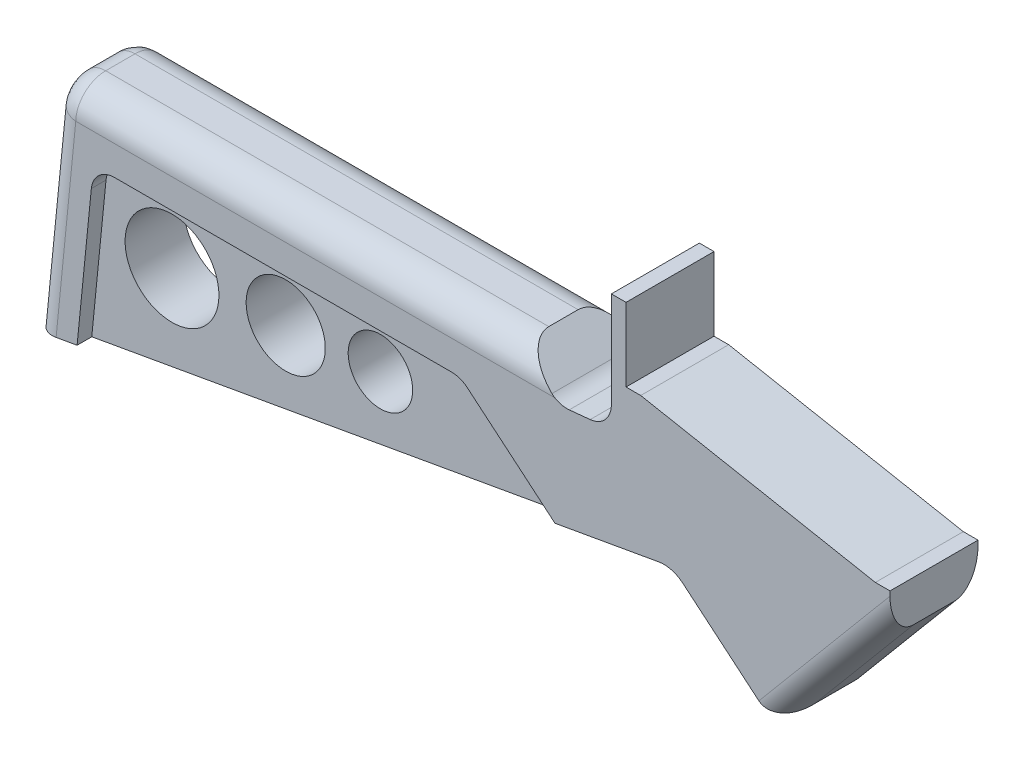
SolidWorks part; units mm, degrees
ref_plane "Front Plane" through (0, 0, 0) normal (0, 0, 1) x (1, 0, 0)
ref_plane "Top Plane" through (0, 0, 0) normal (0, 1, 0) x (1, 0, 0)
ref_plane "Right Plane" through (0, 0, 0) normal (1, 0, 0) x (0, 0, -1)
sketch "Sketch1" plane through (0, 0, 0) normal (0, 0, 1) x (1, 0, 0)
  line L0 (0, 0) -> (85, 0) construction
  line L1 (0, 0) -> (0, 14) construction
  line L2 (0, 14) -> (85, 14) construction
  line L3 (85, 14) -> (85, 0)
  line L4 (80, 14) -> (0, 29.1972)
  line L5 (0, 29.1972) -> (-5, 29.1972)
  line L6 (-5, 29.1972) -> (-5, 54.1972)
  line L7 (-5, 54.1972) -> (-10, 54.1972)
  line L8 (-10, 54.1972) -> (-10, 14.1972)
  line L9 (85, 0) -> (46.4327, -45.9627)
  line L10 (46.4327, -45.9627) -> (10.774, -16.0415)
  line L11 (10.774, -16.0415) -> (-207.4926, -54.7717)
  line L12 (-207.4926, -54.7717) -> (-199.651, 23.8735)
  line L15 (80, 14) -> (85, 14)
  line L16 (-199.651, 23.8735) -> (-41.3345, 23.8735)
  line L17 (-41.3345, 23.8735) -> (-27.713, 12.4437)
  line L18 (-27.713, 12.4437) -> (-10, 14.1972)
  dimension "D1" = 85
  dimension "D2" = 14
  dimension "D3" = 5
  dimension "D4" = 5
  dimension "D5" = 10.756
  dimension "D6" = 50
  dimension "D7" = 60
  dimension "D8" = 5
  dimension "D9" = 80
  dimension "D10" = 40
  dimension "D11" = 25
extrude "Boss-Extrude1" add sketch "Sketch1" along normal blind 15 contours L3 L9 L10 L11 L12 L16 L17 L18 L8 L7 L6 L5 L4 L15
sketch "Sketch2" plane through (0, 0, 0) normal (0, 0, 1) x (1, 0, 0)
  line L0 (10.774, -16.0415) -> (-29.226, -23.1392) construction
  line L1 (10.774, -16.0415) -> (-207.4926, -54.7717) construction
  line L2 (-29.226, -23.1392) -> (-61.4185, 3.8735)
  line L3 (-61.4185, 3.8735) -> (-186.5708, 3.8735)
  line L4 (-186.5708, 3.8735) -> (-192.1467, -52.0487)
  line L5 (-207.4926, -54.7717) -> (-199.651, 23.8735) construction
  line L6 (-199.651, 23.8735) -> (-41.3345, 23.8735) construction
  line L7 (-41.3345, 23.8735) -> (-27.713, 12.4437) construction
  line L8 (-192.1467, -52.0487) -> (-29.226, -23.1392)
  dimension "D1" = 40
  dimension "D2" = 15
  dimension "D3" = 20
extrude "Cut-Extrude1" cut sketch "Sketch2" along normal blind 5
fillet "Fillet1" radius 10 2 edges at (-120.4927, 23.8735, 0) (10.774, -16.0415, 7.5)
fillet "Fillet2" radius 8 9 edges at (-199.651, 23.8735, 12.5) (-199.943, 20.9445, 2.9289) (-204.0703, -20.4491, 0) (65.7164, -22.9813, 0) (46.4327, -45.9627, 7.5) (-186.5708, 3.8735, 2.5) (-61.4185, 3.8735, 2.5) (-10, 14.1972, 7.5) (-27.713, 12.4437, 7.5)
sketch "Sketch3" plane through (0, 0, 5) normal (0, 0, -1) x (-1, 0, 0)
  line L0 (73.9846, -2.1265) -> (179.1682, -2.1265) construction
  line L1 (64.3302, 3.8735) -> (179.3288, 3.8735) construction
  line L2 (64.3302, 3.8735) -> (179.3288, 3.8735) construction
  circle A0 centre (93.7405, -13.1265) radius 11
  circle A1 centre (164.801, -18.1265) radius 16
  circle A2 centre (126.0265, -15.6265) radius 13.5
  dimension "D2" = 22
  dimension "D3" = 32
  dimension "D4" = 27
  dimension "D1" = 6
extrude "Cut-Extrude2" cut sketch "Sketch3" against normal through all
mirror "Mirror1" about plane through (0, 0, 15) normal (0, 0, -1) of bodies 104 102
